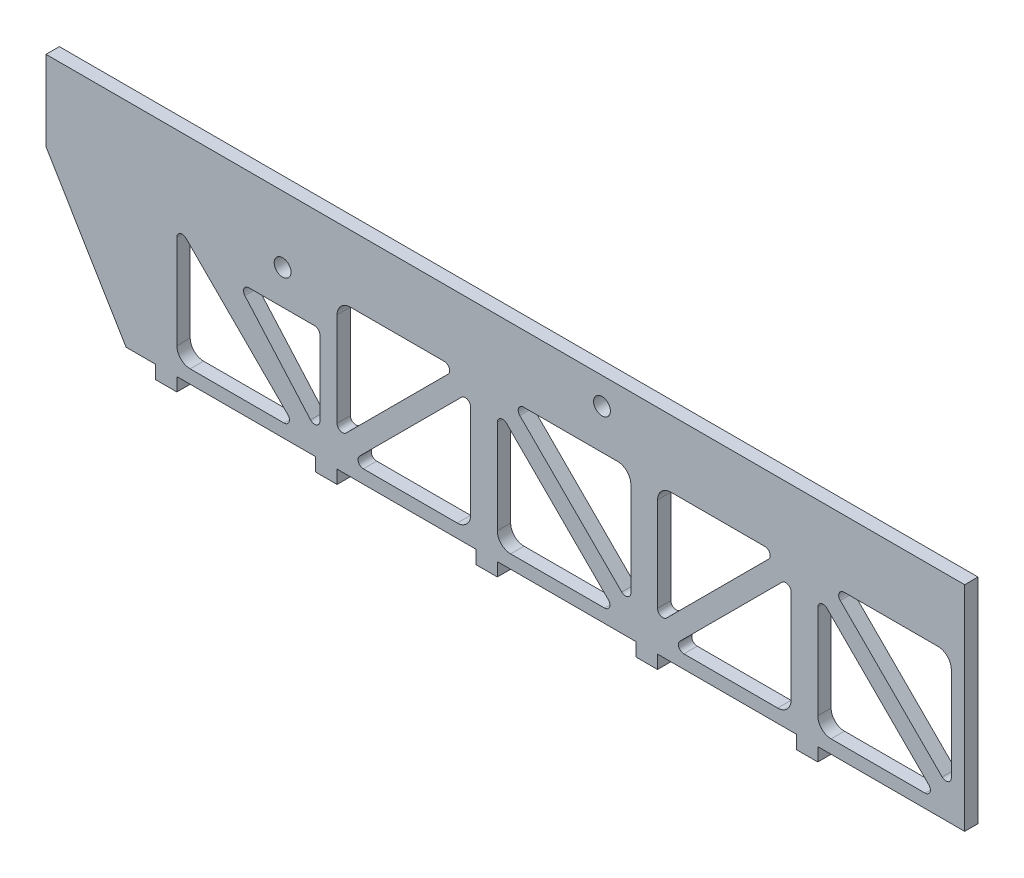
SolidWorks part; units mm, degrees
material "Pine"
ref_plane "Front Plane" through (0, 0, 0) normal (0, 0, 1) x (1, 0, 0)
ref_plane "Top Plane" through (0, 0, 0) normal (0, 1, 0) x (1, 0, 0)
ref_plane "Right Plane" through (0, 0, 0) normal (1, 0, 0) x (0, 0, -1)
sketch "Model" plane through (0, 0, 0) normal (0, 0, 1) x (1, 0, 0)
  line L0 (-306.6281, 15.625) -> (-306.6281, 51.1493)
  line L1 (-309.1681, 53.6893) -> (-340.406, 53.6893)
  line L2 (-342.3135, 49.472) -> (-311.0755, 13.9477)
  line L8 (-171.2321, 6.35) -> (-215.9, 6.35)
  line L9 (-222.25, 57.3679) -> (-222.25, 12.7)
  line L10 (-217.9139, 59.1639) -> (-169.4361, 10.6861)
  line L11 (-234.95, 57.3679) -> (-234.95, 12.7)
  line L12 (-241.3, 6.35) -> (-285.9679, 6.35)
  line L13 (-239.2861, 59.1639) -> (-287.7639, 10.6861)
  line L14 (-294.1139, 17.0361) -> (-245.6361, 65.5139)
  line L15 (-298.45, 63.5) -> (-298.45, 18.8321)
  line L16 (-247.4321, 69.85) -> (-292.1, 69.85)
  line L17 (-323.6321, 6.35) -> (-368.3, 6.35)
  line L18 (-374.65, 57.3679) -> (-374.65, 12.7)
  line L19 (-370.3139, 59.1639) -> (-321.8361, 10.6861)
  line L20 (-18.8321, 6.35) -> (-63.5, 6.35)
  line L21 (-69.85, 57.3679) -> (-69.85, 12.7)
  line L22 (-17.0361, 10.6861) -> (-65.5139, 59.1639)
  line L23 (-82.55, 57.3679) -> (-82.55, 12.7)
  line L24 (-88.9, 6.35) -> (-133.5679, 6.35)
  line L25 (-86.8861, 59.1639) -> (-135.3639, 10.6861)
  line L26 (-93.2361, 65.5139) -> (-141.7139, 17.0361)
  line L27 (-146.05, 63.5) -> (-146.05, 18.8321)
  line L28 (-95.0321, 69.85) -> (-139.7, 69.85)
  line L29 (-163.0861, 17.0361) -> (-211.5639, 65.5139)
  line L30 (-165.1, 69.85) -> (-209.7679, 69.85)
  line L31 (-158.75, 63.5) -> (-158.75, 18.8321)
  line L35 (-398.78, 0) -> (-436.88, 63.5)
  line L36 (0, 0) -> (-398.78, 0)
  line L37 (0, 0) -> (0, 95.25)
  line L38 (0, 95.25) -> (-436.88, 95.25)
  line L39 (-436.88, 63.5) -> (-436.88, 95.25)
  line L40 (-6.35, 63.5) -> (-6.35, 18.8321)
  line L41 (-59.1639, 65.5139) -> (-10.6861, 17.0361)
  line L42 (-12.7, 69.85) -> (-57.3679, 69.85)
  arc A0 (-222.25, 12.7) -> (-215.9, 6.35) centre (-215.9, 12.7) ccw
  arc A1 (-217.9139, 59.1639) -> (-222.25, 57.3679) centre (-219.71, 57.3679) ccw
  arc A2 (-171.2321, 6.35) -> (-169.4361, 10.6861) centre (-171.2321, 8.89) ccw
  arc A3 (-234.95, 57.3679) -> (-239.2861, 59.1639) centre (-237.49, 57.3679) ccw
  arc A4 (-241.3, 6.35) -> (-234.95, 12.7) centre (-241.3, 12.7) ccw
  arc A5 (-287.7639, 10.6861) -> (-285.9679, 6.35) centre (-285.9679, 8.89) ccw
  arc A6 (-245.6361, 65.5139) -> (-247.4321, 69.85) centre (-247.4321, 67.31) ccw
  arc A7 (-298.45, 18.8321) -> (-294.1139, 17.0361) centre (-295.91, 18.8321) ccw
  arc A8 (-292.1, 69.85) -> (-298.45, 63.5) centre (-292.1, 63.5) ccw
  arc A9 (-323.6321, 6.35) -> (-321.8361, 10.6861) centre (-323.6321, 8.89) ccw
  arc A10 (-374.65, 12.7) -> (-368.3, 6.35) centre (-368.3, 12.7) ccw
  arc A11 (-370.3139, 59.1639) -> (-374.65, 57.3679) centre (-372.11, 57.3679) ccw
  arc A12 (-69.85, 12.7) -> (-63.5, 6.35) centre (-63.5, 12.7) ccw
  arc A13 (-65.5139, 59.1639) -> (-69.85, 57.3679) centre (-67.31, 57.3679) ccw
  arc A14 (-18.8321, 6.35) -> (-17.0361, 10.6861) centre (-18.8321, 8.89) ccw
  arc A15 (-82.55, 57.3679) -> (-86.8861, 59.1639) centre (-85.09, 57.3679) ccw
  arc A16 (-88.9, 6.35) -> (-82.55, 12.7) centre (-88.9, 12.7) ccw
  arc A17 (-135.3639, 10.6861) -> (-133.5679, 6.35) centre (-133.5679, 8.89) ccw
  arc A18 (-93.2361, 65.5139) -> (-95.0321, 69.85) centre (-95.0321, 67.31) ccw
  arc A19 (-146.05, 18.8321) -> (-141.7139, 17.0361) centre (-143.51, 18.8321) ccw
  arc A20 (-139.7, 69.85) -> (-146.05, 63.5) centre (-139.7, 63.5) ccw
  arc A21 (-163.0861, 17.0361) -> (-158.75, 18.8321) centre (-161.29, 18.8321) ccw
  arc A22 (-209.7679, 69.85) -> (-211.5639, 65.5139) centre (-209.7679, 67.31) ccw
  arc A23 (-158.75, 63.5) -> (-165.1, 69.85) centre (-165.1, 63.5) ccw
  arc A24 (-306.6281, 15.625) -> (-311.0755, 13.9477) centre (-309.1681, 15.625) cw
  arc A25 (-340.406, 53.6893) -> (-342.3135, 49.472) centre (-340.406, 51.1493) ccw
  arc A26 (-306.6281, 51.1493) -> (-309.1681, 53.6893) centre (-309.1681, 51.1493) ccw
  arc A27 (-10.6861, 17.0361) -> (-6.35, 18.8321) centre (-8.89, 18.8321) ccw
  arc A28 (-57.3679, 69.85) -> (-59.1639, 65.5139) centre (-57.3679, 67.31) ccw
  arc A29 (-6.35, 63.5) -> (-12.7, 69.85) centre (-12.7, 63.5) ccw
  circle A30 centre (-172.466, 88.9) radius 4
  circle A31 centre (-324.358, 70.104) radius 4
  dimension "D2" = 172.466
  dimension "D4" = 8
  dimension "D5" = 151.892
  dimension "D7" = 8
  dimension "D6" = 18.796
  dimension "D8" = 2.54
  dimension "D1" = 95.25
  dimension "D3" = 6.35
extrude "Boss-Extrude1" add sketch "Model" along normal blind 6.35
sketch "Sketch1" plane through (0, 0, 6.35) normal (0, 0, 1) x (1, 0, 0)
  line L0 (-69.85, 95.25) -> (-69.85, 0) construction
  line L1 (-69.85, 57.3679) -> (-69.85, 12.7) construction
  line L2 (-398.78, 0) -> (0, 0) construction
  line L3 (-146.05, 95.25) -> (-146.05, 0) construction
  line L4 (-146.05, 63.5) -> (-146.05, 18.8321) construction
  line L5 (-222.25, 95.25) -> (-222.25, 0) construction
  line L6 (-222.25, 57.3679) -> (-222.25, 12.7) construction
  line L7 (-298.45, 95.25) -> (-298.45, 0) construction
  line L8 (-298.45, 63.5) -> (-298.45, 18.8321) construction
  line L9 (-374.65, 95.25) -> (-374.65, 0) construction
  line L10 (-374.65, 57.3679) -> (-374.65, 12.7) construction
  line L11 (0, 95.25) -> (-436.88, 95.25) construction
  line L12 (-69.85, 0) -> (-80.01, 0)
  line L13 (-69.85, 0) -> (-69.85, -6.35)
  line L14 (-69.85, -6.35) -> (-80.01, -6.35)
  line L15 (-80.01, 0) -> (-80.01, -6.35)
  line L16 (-146.05, 0) -> (-156.21, 0)
  line L17 (-146.05, 0) -> (-146.05, -6.35)
  line L18 (-146.05, -6.35) -> (-156.21, -6.35)
  line L19 (-156.21, 0) -> (-156.21, -6.35)
  line L20 (-222.25, 0) -> (-232.41, 0)
  line L21 (-222.25, 0) -> (-222.25, -6.35)
  line L22 (-222.25, -6.35) -> (-232.41, -6.35)
  line L23 (-232.41, 0) -> (-232.41, -6.35)
  line L24 (-298.45, 0) -> (-308.61, 0)
  line L25 (-298.45, 0) -> (-298.45, -6.35)
  line L26 (-298.45, -6.35) -> (-308.61, -6.35)
  line L27 (-308.61, 0) -> (-308.61, -6.35)
  line L28 (-374.65, 0) -> (-384.81, 0)
  line L29 (-374.65, 0) -> (-374.65, -6.35)
  line L30 (-374.65, -6.35) -> (-384.81, -6.35)
  line L31 (-384.81, 0) -> (-384.81, -6.35)
  line L32 (0, 0) -> (0, 95.25) construction
  line L53 (-436.88, 95.25) -> (0, 95.25)
  line L54 (-436.88, 95.25) -> (-436.88, 101.6)
  line L55 (-436.88, 101.6) -> (0, 101.6)
  line L56 (0, 95.25) -> (0, 101.6)
  point P37 (-69.85, 95.25)
  point P40 (-146.05, 95.25)
  point P41 (-222.25, 95.25)
  point P56 (-27.6534, 101.6)
  dimension "D1" = 6.35
  dimension "D2" = 10.16
  dimension "D3" = 10.16
  dimension "D4" = 10.16
  dimension "D5" = 10.16
  dimension "D6" = 10.16
  dimension "D8" = 6.35
extrude "Boss-Extrude2" add sketch "Sketch1" against normal up to surface (6.35 mm away) up to face at (-168.466, 88.9, 0)
equation "\"thick\"=0.25"
equation "\"D1@Boss-Extrude1\"=\"thick\""
